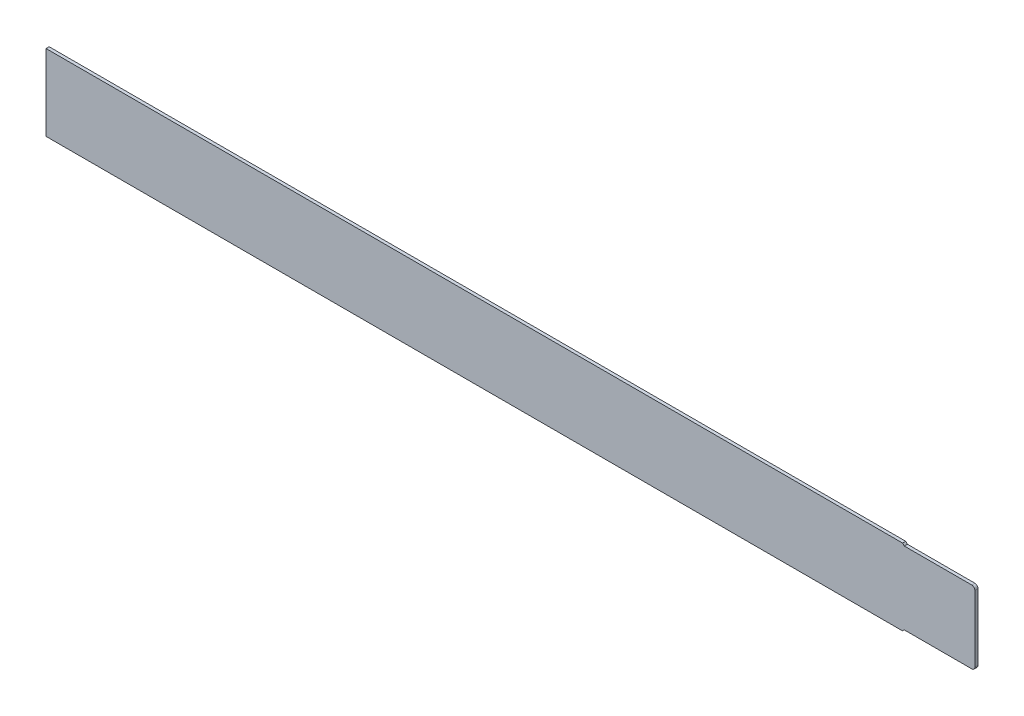
SolidWorks part; units mm, degrees
ref_plane "Front Plane" through (0, 0, 0) normal (0, 0, 1) x (1, 0, 0)
ref_plane "Top Plane" through (0, 0, 0) normal (0, 1, 0) x (1, 0, 0)
ref_plane "Right Plane" through (0, 0, 0) normal (1, 0, 0) x (0, 0, -1)
sketch "Sketch1" plane through (0, 0, 0) normal (0, 0, 1) x (1, 0, 0)
  line L0 (0, 3.666) -> (-82.5, 3.666)
  line L5 (0.9095, 0) -> (-0.9095, 0) construction
  line L6 (0, -3.666) -> (-82.5, -3.666)
  line L7 (-82.5, -3.666) -> (-82.5, 3.666)
  line L8 (0, -0.9081) -> (0, 0.9081) construction
  line L9 (0, 3.666) -> (0, 3.5)
  line L10 (0, 3.5) -> (7, 3.5)
  line L11 (0, -3.5) -> (7, -3.5)
  line L12 (0, -3.666) -> (0, -3.5)
  line L13 (7, 3.5) -> (7, -3.5)
  point P14 (7.8175, 3.0145)
  dimension "D1" = 7.332
  dimension "D2" = 82.5
  dimension "D3" = 7
  dimension "D4" = 7
extrude "Boss-Extrude1" add sketch "Sketch1" along normal blind 0.3
fillet "Fillet1" radius 0.3 2 edges at (7, 3.5, 0.15) (7, -3.5, 0.15)
chamfer "Chamfer1" distance 0.2 angle 45 2 edges at (0, 3.5, 0.15) (0, -3.5, 0.15)
